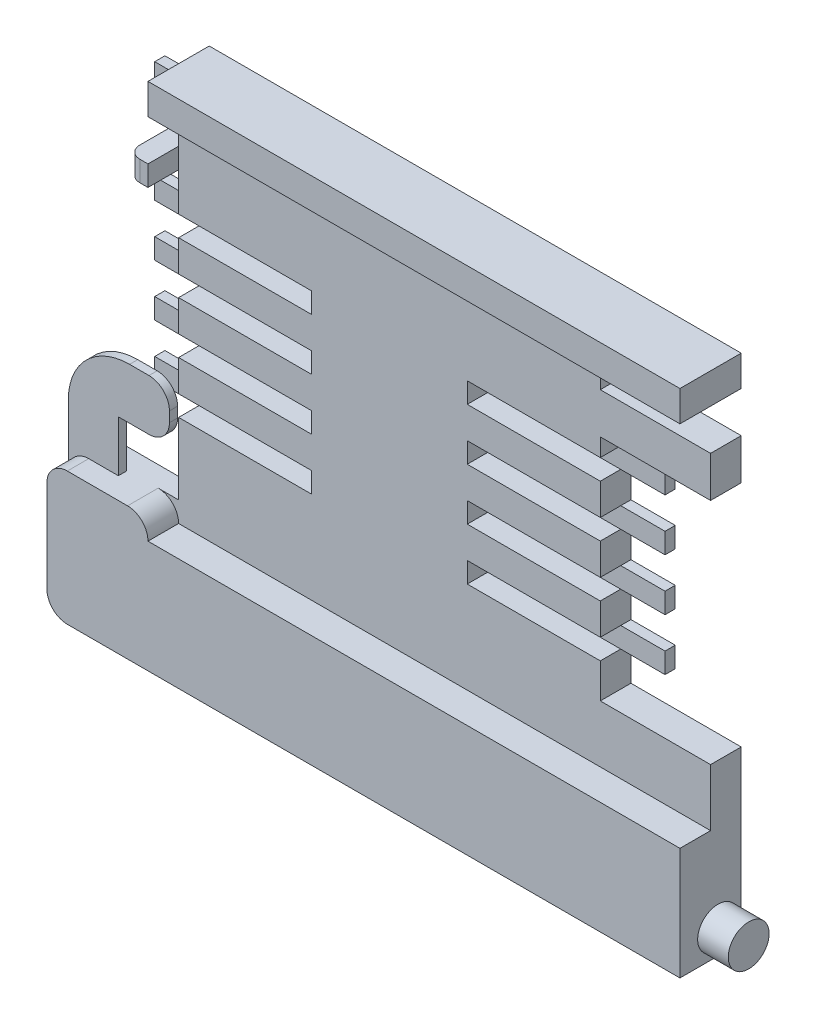
SolidWorks part; units mm, degrees
ref_plane "Front Plane" through (0, 0, 0) normal (0, 0, 1) x (1, 0, 0)
ref_plane "Top Plane" through (0, 0, 0) normal (0, 1, 0) x (1, 0, 0)
ref_plane "Right Plane" through (0, 0, 0) normal (1, 0, 0) x (0, 0, -1)
sketch "Эскиз1" plane through (0, 0, 0) normal (0, 0, 1) x (1, 0, 0)
  line L1 (13.025, -12.5) -> (-13.025, -12.5)
  line L2 (13.025, -12.5) -> (13.025, 12.5)
  line L3 (13.025, 12.5) -> (-13.025, 12.5)
  line L4 (-13.025, -12.5) -> (-13.025, 12.5)
  line L5 (13.025, -12.5) -> (-13.025, 12.5) construction
  line L6 (13.025, 12.5) -> (-13.025, -12.5) construction
  point P0 (0, 0)
  dimension "D1" = 26.05
  dimension "D2" = 25
extrude "Бобышка-Вытянуть1" add sketch "Эскиз1" along normal blind 1.5
sketch "Эскиз3" plane through (0, 0, 1.5) normal (0, 0, 1) x (1, 0, 0)
  line L0 (13.025, -12.5) -> (13.025, 12.5) construction
  line L1 (13.025, 7) -> (7.625, 7)
  line L2 (13.025, 7) -> (13.025, -4.2)
  line L3 (13.025, -4.2) -> (7.625, -4.2)
  line L4 (7.625, 7) -> (7.625, -4.2)
  line L5 (-13.025, 12.5) -> (-13.025, -12.5) construction
  line L6 (13.025, 12.5) -> (-13.025, 12.5) construction
  dimension "D1" = 11.2
  dimension "D2" = 20.65
  dimension "D3" = 5.5
extrude "Вырез-Вытянуть1" cut sketch "Эскиз3" against normal through all
sketch "Эскиз4" plane through (0, 0, 1.5) normal (0, 0, 1) x (1, 0, 0)
  line L0 (13.025, 7) -> (13.025, 12.5) construction
  line L1 (-13.025, 12.5) -> (13.025, 12.5)
  line L2 (-13.025, 12.5) -> (-13.025, 11)
  line L3 (-13.025, 11) -> (13.025, 11)
  line L4 (13.025, 12.5) -> (13.025, 11)
  dimension "D1" = 1.5
extrude "Бобышка-Вытянуть2" add sketch "Эскиз4" along normal blind 1.5
sketch "Эскиз5" plane through (0, 0, 1.5) normal (0, 0, 1) x (1, 0, 0)
  line L1 (13.025, 11) -> (7.625, 11)
  line L2 (13.025, 11) -> (13.025, 9)
  line L3 (13.025, 9) -> (7.625, 9)
  line L4 (7.625, 11) -> (7.625, 9)
  dimension "D1" = 2
extrude "Вырез-Вытянуть2" cut sketch "Эскиз5" against normal through all
sketch "Эскиз6" plane through (0, 0, 1.5) normal (0, 0, 1) x (1, 0, 0)
  line L1 (13.025, -12.5) -> (-17.975, -12.5)
  line L2 (13.025, -12.5) -> (13.025, -7)
  line L3 (13.025, -7) -> (-17.975, -7)
  line L4 (-17.975, -12.5) -> (-17.975, -7)
  dimension "D1" = 5.5
  dimension "D2" = 31
extrude "Бобышка-Вытянуть3" add sketch "Эскиз6" along normal blind 1.5
sketch "Эскиз7" plane through (13.025, 0, 0) normal (1, 0, 0) x (0, 0, -1)
  circle A0 centre (-1.133, -11.3014) radius 1
  point P2 (-1.133, -11.3014)
  dimension "D1" = 2
extrude "Бобышка-Вытянуть4" add sketch "Эскиз7" along normal blind 1.5
sketch "Эскиз10" plane through (0, 0, 1.5) normal (0, 0, -1) x (-1, 0, 0)
  line L0 (13.025, 12.5) -> (13.025, -12.5) construction
  line L1 (17.975, -12.5) -> (13.025, -12.5)
  line L2 (17.975, -12.5) -> (17.975, -6)
  line L3 (17.975, -6) -> (13.025, -6)
  line L4 (13.025, -12.5) -> (13.025, -6)
  dimension "D1" = 6.5
extrude "Бобышка-Вытянуть13" add sketch "Эскиз10" along normal blind 1 and the other way blind 1.5
fillet "Скругление1" radius 1 3 edges at (-17.975, -12.5, 1.75) (-17.975, -6, 1.75) (-13.025, -6, 2.25)
sketch "Эскиз11" plane through (0, -6, 0) normal (0, 1, 0) x (1, 0, 0)
  line L0 (-17.975, -1.75) -> (-13.025, -1.75)
  line L1 (-17.975, -3) -> (-17.975, -0.5) construction
  line L2 (-13.025, -3) -> (-13.025, 0) construction
extrude "Вытянуть-Тонкостенный1" add sketch "Эскиз11" along normal blind 5 thin thin type mid plane wall 0.4
sketch "Эскиз12" plane through (0, 0, 1.95) normal (0, 0, 1) x (1, 0, 0)
  line L1 (-13.025, -6) -> (-15.525, -6)
  line L2 (-13.025, -6) -> (-13.025, -3.5)
  line L3 (-13.025, -3.5) -> (-15.525, -3.5)
  line L4 (-15.525, -6) -> (-15.525, -3.5)
  dimension "D1" = 2.5
  dimension "D2" = 2.5
extrude "Вырез-Вытянуть3" cut sketch "Эскиз12" against normal through all
fillet "Скругление2" radius 3 1 edges at (-17.975, -1, 1.75)
fillet "Скругление3" radius 1 2 edges at (-13.025, -3.5, 1.75) (-13.025, -1, 1.75)
sketch "Эскиз13" plane through (0, -6, 0) normal (0, -1, 0) x (1, 0, 0)
  line L1 (-16.975, 1.95) -> (-17.975, 1.95)
  line L2 (-16.975, 1.95) -> (-16.975, 1.55)
  line L3 (-16.975, 1.55) -> (-17.975, 1.55)
  line L4 (-17.975, 1.95) -> (-17.975, 1.55)
extrude "Бобышка-Вытянуть14" add sketch "Эскиз13" along normal blind 4
sketch "Эскиз15" plane through (-13.025, 0, 0) normal (-1, 0, 0) x (0, 0, 1)
  line L0 (0, 12.5) -> (0, -12.5) construction
  line L1 (0, 9) -> (1.5, 9)
  line L2 (0, 9) -> (0, 8)
  line L3 (0, 8) -> (1.5, 8)
  line L4 (1.5, 9) -> (1.5, 8)
  line L5 (1.5, 11) -> (1.5, -6) construction
  dimension "D1" = 1
  dimension "D2" = 3.5
extrude "Бобышка-Вытянуть15" add sketch "Эскиз15" along normal blind 1
sketch "Эскиз16" plane through (0, 0, 1.5) normal (0, 0, 1) x (1, 0, 0)
  line L1 (-13.025, 8) -> (-14.025, 8)
  line L2 (-13.025, 8) -> (-13.025, 9)
  line L3 (-13.025, 9) -> (-14.025, 9)
  line L4 (-14.025, 8) -> (-14.025, 9)
extrude "Бобышка-Вытянуть16" add sketch "Эскиз16" along normal blind 1.5
sketch "Эскиз17" plane through (0, 0, 1.5) normal (0, 0, 1) x (1, 0, 0)
  line L0 (-13.025, -2) -> (-6.51, -2)
  line L1 (-13.025, 8) -> (-13.025, -6) construction
  line L4 (7.625, -2) -> (1.11, -2)
  line L5 (7.625, 7) -> (7.625, -4.2) construction
  line L6 (-13.025, 0.54) -> (-6.51, 0.54)
  line L7 (7.625, 0.54) -> (1.11, 0.54)
  line L8 (-13.025, 3.08) -> (-6.51, 3.08)
  line L9 (7.625, 3.08) -> (1.11, 3.08)
  line L10 (-13.025, 5.62) -> (-6.51, 5.62)
  line L11 (7.625, 5.62) -> (1.11, 5.62)
  dimension "D1" = 7.62
  dimension "D2" = 10.5
  dimension "D3" = 4
extrude "Вырез-Вытянуть-Тонкостенный1" cut sketch "Эскиз17" against normal blind 1 thin thin type mid plane wall 1
sketch "Эскиз18" plane through (7.625, 0, 0) normal (1, 0, 0) x (0, 0, -1)
  line L0 (-1.5, 5.12) -> (0, 5.12) construction
  line L1 (0, 7) -> (0, -4.2) construction
  line L2 (-0.5, 3.58) -> (0, 3.58)
  line L3 (-0.5, 6.12) -> (0, 6.12)
  line L4 (-0.5, 6.12) -> (-0.5, 5.12)
  line L5 (-0.5, 5.12) -> (0, 5.12)
  line L6 (0, 6.12) -> (0, 5.12)
  line L7 (-0.5, 3.58) -> (-0.5, 2.58)
  line L8 (-0.5, 2.58) -> (0, 2.58)
  line L9 (0, 3.58) -> (0, 2.58)
  line L10 (-0.5, 1.04) -> (0, 1.04)
  line L11 (-0.5, 1.04) -> (-0.5, 0.04)
  line L12 (-0.5, 0.04) -> (0, 0.04)
  line L13 (0, 1.04) -> (0, 0.04)
  line L14 (-0.5, -1.5) -> (0, -1.5)
  line L15 (-0.5, -1.5) -> (-0.5, -2.5)
  line L16 (-0.5, -2.5) -> (0, -2.5)
  line L17 (0, -1.5) -> (0, -2.5)
  dimension "D1" = 4
extrude "Бобышка-Вытянуть17" add sketch "Эскиз18" along normal blind 2.17
sketch "Эскиз20" plane through (-13.025, 0, 0) normal (-1, 0, 0) x (0, 0, 1)
  line L0 (1.5, 5.12) -> (0, 5.12) construction
  line L1 (0.5, 3.58) -> (0, 3.58)
  line L2 (0.5, 6.12) -> (0, 6.12)
  line L3 (0.5, 6.12) -> (0.5, 5.12)
  line L4 (0.5, 5.12) -> (0, 5.12)
  line L5 (0, 6.12) -> (0, 5.12)
  line L6 (0.5, 3.58) -> (0.5, 2.58)
  line L7 (0.5, 2.58) -> (0, 2.58)
  line L8 (0, 3.58) -> (0, 2.58)
  line L9 (0.5, 1.04) -> (0, 1.04)
  line L10 (0.5, 1.04) -> (0.5, 0.04)
  line L11 (0.5, 0.04) -> (0, 0.04)
  line L12 (0, 1.04) -> (0, 0.04)
  line L13 (0.5, -1.5) -> (0, -1.5)
  line L14 (0.5, -1.5) -> (0.5, -2.5)
  line L15 (0.5, -2.5) -> (0, -2.5)
  line L16 (0, -1.5) -> (0, -2.5)
  dimension "D1" = 4
extrude "Бобышка-Вытянуть18" add sketch "Эскиз20" along normal blind 2.17
sketch "Эскиз21" plane through (0, 0, 1.5) normal (0, 0, 1) x (1, 0, 0)
  line L0 (-6.51, -2.5) -> (-6.51, 11) construction
  line L1 (-13.025, 11) -> (13.025, 11) construction
  line L2 (1.11, -2.5) -> (1.11, 11) construction
  line L3 (7.625, -2.5) -> (1.11, -2.5) construction
  line L4 (1.11, -2.5) -> (1.11, -1.5) construction
  line L5 (-13.025, 11) -> (-13.025, 9) construction
  line L6 (-6.51, 11) -> (-13.025, 11)
  line L7 (-6.51, 11) -> (-6.51, 10)
  line L8 (-6.51, 10) -> (-13.025, 10)
  line L9 (-13.025, 11) -> (-13.025, 10)
  line L10 (7.625, 11) -> (7.625, 9) construction
  line L11 (1.11, 11) -> (7.625, 11)
  line L12 (1.11, 11) -> (1.11, 9.9047)
  line L13 (1.11, 9.9047) -> (7.625, 9.9047)
  line L14 (7.625, 11) -> (7.625, 9.9047)
  dimension "D1" = 1
extrude "Вырез-Вытянуть4" cut sketch "Эскиз21" against normal blind 1
sketch "Эскиз22" plane through (-13.025, 0, 0) normal (-1, 0, 0) x (0, 0, 1)
  line L0 (0, 12.5) -> (0, 9) construction
  line L1 (0, 11) -> (0.5, 11)
  line L2 (0, 11) -> (0, 10)
  line L3 (0, 10) -> (0.5, 10)
  line L4 (0.5, 11) -> (0.5, 10)
extrude "Бобышка-Вытянуть19" add sketch "Эскиз22" along normal blind 2.17
sketch "Эскиз23" plane through (7.625, 0, 0) normal (1, 0, 0) x (0, 0, -1)
  line L1 (0, 11) -> (-0.5, 11)
  line L2 (0, 11) -> (0, 9.9047)
  line L3 (0, 9.9047) -> (-0.5, 9.9047)
  line L4 (-0.5, 11) -> (-0.5, 9.9047)
extrude "Бобышка-Вытянуть20" add sketch "Эскиз23" along normal blind 2.17
fillet "Скругление4" radius 0.6 1 edges at (-14.025, 8.5, 3)
